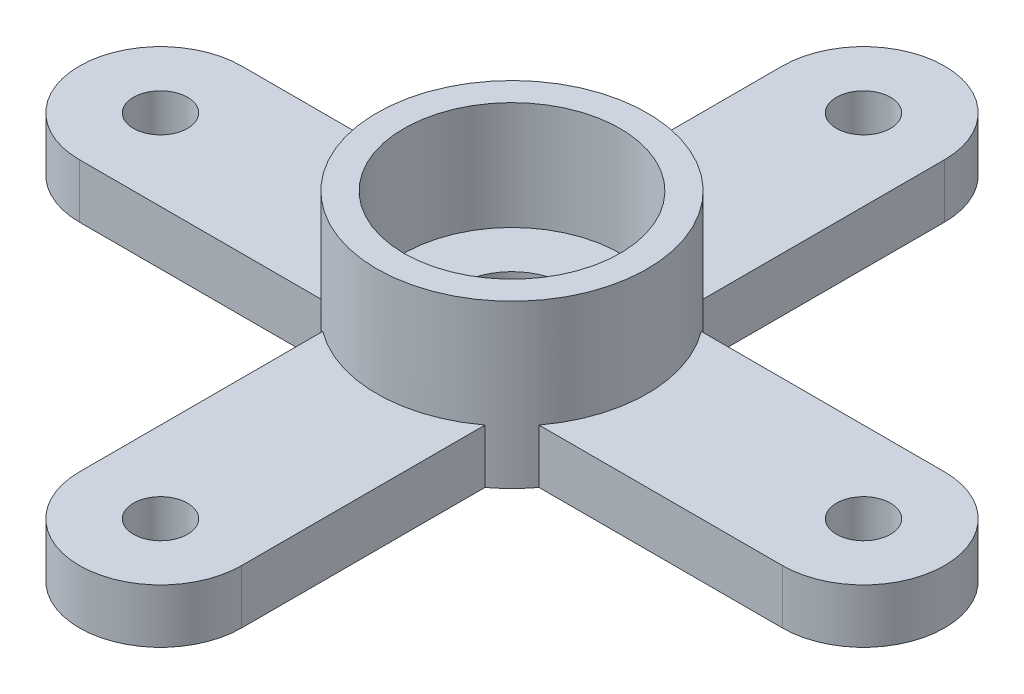
SolidWorks part; units mm, degrees
ref_plane "Front Plane" through (0, 0, 0) normal (0, 0, 1) x (1, 0, 0)
ref_plane "Top Plane" through (0, 0, 0) normal (0, 1, 0) x (1, 0, 0)
ref_plane "Right Plane" through (0, 0, 0) normal (1, 0, 0) x (0, 0, -1)
sketch "Sketch4" plane through (0, 0, 0) normal (0, 1, 0) x (1, 0, 0)
  line L0 (0, 0) -> (6.5, 0) construction
  line L1 (6.5, 1.5) -> (2, 1.5) construction
  line L2 (6.5, -1.5) -> (2, -1.5) construction
  line L3 (6.5, 1.5) -> (2, 1.5)
  line L4 (2, -1.5) -> (6.5, -1.5)
  line L5 (1.5, -6.5) -> (1.5, -2)
  line L6 (-1.5, -2) -> (-1.5, -6.5)
  line L7 (-6.5, -1.5) -> (-2, -1.5)
  line L8 (-2, 1.5) -> (-6.5, 1.5)
  line L9 (-1.5, 6.5) -> (-1.5, 2)
  line L10 (1.5, 2) -> (1.5, 6.5)
  circle A0 centre (0, 0) radius 2.5
  circle A1 centre (0, 0) radius 2
  circle A2 centre (6.5, 0) radius 1.5
  circle A3 centre (6.5, 0) radius 0.5
  circle A4 centre (0, 0) radius 1
  circle A5 centre (0, -6.5) radius 1.5
  circle A6 centre (0, -6.5) radius 0.5
  circle A7 centre (-6.5, 0) radius 1.5
  circle A8 centre (-6.5, 0) radius 0.5
  circle A9 centre (0, 6.5) radius 1.5
  circle A10 centre (0, 6.5) radius 0.5
  point P36 (0, 0)
  dimension "D1" = 4
extrude "Boss-Extrude1" add sketch "Sketch4" along normal blind 1 contours A9 A10 | A9 L9 A0 L10 | A2 L3 A0 L4 | A2 A3 | A0 A1 | A1 A4 | A7 A8 | A7 L7 A0 L8 | A5 L5 A0 L6 | A5 A6 region at (3.8465, 0, 0) region at (7.5307, 0, -1.0307) region at (2.3046, 0, -0.7682) region at (0, 0, -3.8465) region at (0, 0, -5.0424) region at (0, 0, 3.8465) region at (-3.8465, 0, 0) region at (0, 0, 7.9576) region at (-5.4693, 0, -1.0307) region at (-1.9434, 0, 0)
extrude "Boss-Extrude2" add sketch "Sketch4<3>" along normal blind 3 contours A0 | A1
sketch "Sketch4<3>" plane through (0, 0, 0) normal (0, 1, 0) x (1, 0, 0) same geometry as "Sketch4"
